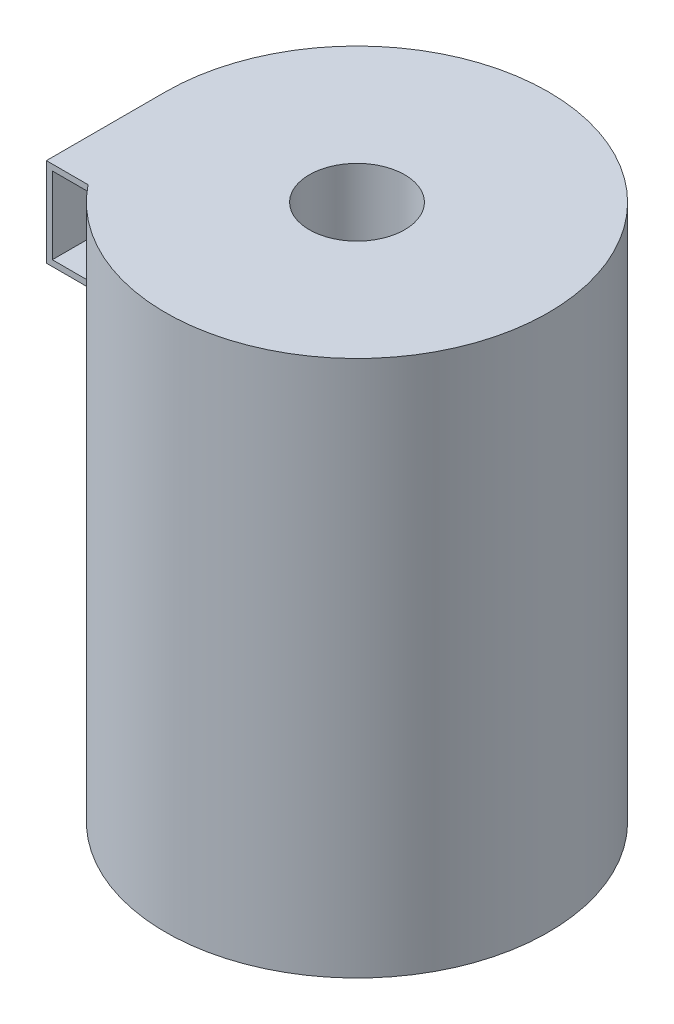
SolidWorks part; units mm, degrees
ref_plane "정면" through (0, 0, 0) normal (0, 0, 1) x (1, 0, 0)
ref_plane "윗면" through (0, 0, 0) normal (0, 1, 0) x (1, 0, 0)
ref_plane "우측면" through (0, 0, 0) normal (1, 0, 0) x (0, 0, -1)
sketch "스케치3" plane through (0, 0, 0) normal (0, 0, 1) x (1, 0, 0)
  line L0 (0, 0) -> (0, 24.4556) construction
  line L1 (0, 0) -> (17.168, 0) construction
  line L2 (0, 19) -> (8, 19)
  line L3 (8, 19) -> (8, 90)
  line L4 (8, 90) -> (32.1, 90)
  line L5 (32.1, 90) -> (32.1, 0)
  line L6 (32.1, 0) -> (0, 0)
  line L7 (0, 0) -> (0, 19)
  dimension "D1" = 32.1
  dimension "D2" = 8
  dimension "D3" = 71
  dimension "D4" = 90
revolve "회전1" add sketch "스케치3" angle 360 about L0
sketch "스케치4" plane through (0, 0, 0) normal (0, 0, 1) x (1, 0, 0)
  line L1 (-32.1, 90) -> (-23.1, 90)
  line L2 (-32.1, 90) -> (-32.1, 75.1)
  line L3 (-32.1, 75.1) -> (-23.1, 75.1)
  line L4 (-23.1, 90) -> (-23.1, 75.1)
  dimension "D1" = 14.9
  dimension "D2" = 9
extrude "보스-돌출3" add sketch "스케치4" along normal blind 20
shell "쉘2" thickness 1 removed face at (0, 0, -32.1) removed face at (-28.604, 82.55, 20) removed face at (0, 19, -8)
